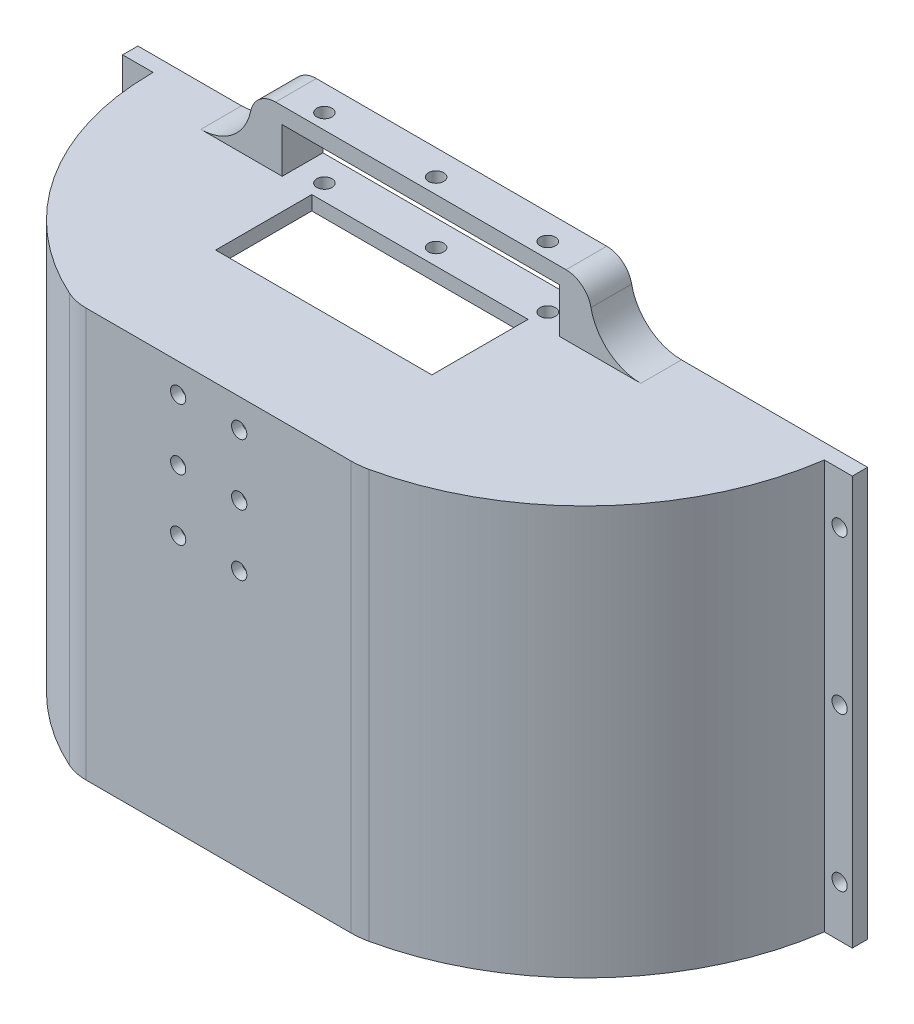
SolidWorks part; units mm, degrees
ref_plane "前视基准面" through (0, 0, 0) normal (0, 0, 1) x (1, 0, 0)
ref_plane "上视基准面" through (0, 0, 0) normal (0, 1, 0) x (1, 0, 0)
ref_plane "右视基准面" through (0, 0, 0) normal (1, 0, 0) x (0, 0, -1)
other "Configuration Table"
sketch "草图1" plane through (0, 0, 0) normal (0, 0, 1) x (1, 0, 0)
  line L0 (-77.3109, 43.4948) -> (-77.3109, -31.0552) construction
  line L1 (-77.3109, -31.0552) -> (50.1101, -31.0552) construction
  line L2 (50.1101, 43.4948) -> (-98.3152, 43.4948) construction
  line L3 (50.1101, -31.0552) -> (50.1101, 43.4948) construction
  line L4 (-85.3152, -34.0552) -> (58.1101, -34.0552)
  line L5 (58.1101, -34.0552) -> (58.1101, 46.2948)
  line L6 (58.1101, 46.2948) -> (-85.3152, 46.2948)
  line L7 (-85.3152, 46.2948) -> (-85.3152, -34.0552)
  line L8 (-85.3152, -34.0552) -> (58.1101, -34.0552)
  line L9 (58.1101, -34.0552) -> (58.1101, 46.2948)
  line L10 (58.1101, 46.2948) -> (-85.3152, 46.2948)
  line L11 (-85.3152, 46.2948) -> (-85.3152, -34.0552)
  line L12 (-77.3109, 43.4948) -> (-77.3109, -31.0552)
  line L13 (-77.3109, -31.0552) -> (50.1101, -31.0552)
  line L14 (50.1101, 43.4948) -> (-77.3109, 43.4948)
  line L15 (50.1101, -31.0552) -> (50.1101, 43.4948)
  circle A0 centre (55.6101, -24.0552) radius 1.5 construction
  circle A1 centre (55.6101, 6.1198) radius 1.5 construction
  circle A2 centre (55.6101, 36.2948) radius 1.5 construction
  circle A3 centre (-82.8109, -24.0552) radius 1.5 construction
  circle A4 centre (-82.8109, 6.1198) radius 1.5 construction
  circle A5 centre (-82.8109, 36.2948) radius 1.5 construction
  circle A6 centre (55.6101, -24.0552) radius 1.5
  circle A7 centre (55.6101, 6.1198) radius 1.5
  circle A8 centre (55.6101, 36.2948) radius 1.5
  circle A9 centre (-82.8109, -24.0552) radius 1.5
  circle A10 centre (-82.8109, 6.1198) radius 1.5
  circle A11 centre (-82.8109, 36.2948) radius 1.5
  dimension "D1" = 0
extrude "凸台-拉伸1" add sketch "草图1" along normal blind 3
sketch "草图2" plane through (0, 46.2948, 0) normal (0, 1, 0) x (1, 0, 0)
  line L0 (58.1101, -3) -> (-85.3152, -3) construction
  line L1 (52.1101, -3) -> (-79.3152, -3)
  line L2 (52.1101, -3) -> (52.1101, -8)
  line L3 (52.1101, -8) -> (-79.3152, -8)
  line L4 (-79.3152, -3) -> (-79.3152, -8)
  line L5 (58.1101, -3) -> (58.1101, 0) construction
  line L6 (-85.3152, -3) -> (-85.3152, 0) construction
  line L7 (-21.7025, -953.5) -> (-21.7025, 49046.5) construction
  line L8 (-52.0899, 46.5) -> (8.6848, 46.5) construction
  circle A0 centre (-21.7025, -5) radius 1.5
  point P15 (-21.7025, 46.5)
  dimension "D5" = 3
  dimension "D1" = 6
  dimension "D2" = 6
  dimension "D3" = 5
  dimension "D4" = 2
extrude "凸台-拉伸2" add sketch "草图2" against normal blind 2.8
sketch "草图3" plane through (0, 46.2948, 0) normal (0, 1, 0) x (1, 0, 0)
  line L0 (-999.7596, -5) -> (49000.2404, -5) construction
  circle A0 centre (0.2404, -5) radius 1.5
  circle A1 centre (-43.6455, -5) radius 1.5
  dimension "D1" = 3
  dimension "D2" = 3
extrude "切除-拉伸1" cut sketch "草图3" against normal blind 10
sketch "草图4" plane through (0, 46.2948, 0) normal (0, 1, 0) x (1, 0, 0)
  line L0 (-77.3109, 0) -> (50.1101, 0) construction
  line L1 (5.5404, 0) -> (11.5404, 0)
  line L2 (5.5404, 0) -> (5.5404, -8)
  line L3 (5.5404, -8) -> (11.5404, -8)
  line L4 (11.5404, 0) -> (11.5404, -8)
  line L5 (-79.3152, -8) -> (52.1101, -8) construction
  line L6 (5.2404, -16.5556) -> (5.2404, 0) construction
  line L7 (-48.9455, 0) -> (-54.9455, 0)
  line L8 (-48.9455, 0) -> (-48.9455, -8)
  line L9 (-48.9455, -8) -> (-54.9455, -8)
  line L10 (-54.9455, 0) -> (-54.9455, -8)
  line L11 (-48.6455, 0) -> (-48.6455, -16.5556) construction
  dimension "D1" = 6
  dimension "D2" = 6
  dimension "D3" = 0.3
  dimension "D4" = 0.3
extrude "凸台-拉伸3" add sketch "草图4" along normal blind 10
sketch "草图5" plane through (0, 56.2948, 0) normal (0, 1, 0) x (1, 0, 0)
  line L1 (5.5404, -8) -> (-48.9455, -8)
  line L2 (5.5404, -8) -> (5.5404, 0)
  line L3 (5.5404, 0) -> (-48.9455, 0)
  line L4 (-48.9455, -8) -> (-48.9455, 0)
extrude "凸台-拉伸4" add sketch "草图5" against normal blind 1.2
fillet "圆角1" radius 10 2 edges at (11.5404, 46.2948, 4) (-54.9455, 46.2948, 4)
sketch "草图6" plane through (0, 56.2948, 0) normal (0, 1, 0) x (1, 0, 0)
  circle A0 centre (0.2404, -5) radius 1.5
  circle A1 centre (-21.7025, -5) radius 1.5
  circle A2 centre (-43.6455, -5) radius 1.5
  dimension "D1" = 3
  dimension "D2" = 3
  dimension "D3" = 3
extrude "切除-拉伸2" cut sketch "草图6" against normal blind 3
sketch "草图7" plane through (0, 46.2948, 0) normal (0, 1, 0) x (1, 0, 0)
  line L0 (-47.8552, -50) -> (4.4502, -50) construction
  line L1 (-47.8552, -50) -> (4.4502, -50) construction
  line L2 (52.1101, -3) -> (-79.3152, -3)
  line L3 (-45.8212, -49.7) -> (3.801, -49.7)
  line L4 (-47.8552, -49.7) -> (4.4502, -49.7) construction
  arc A0 (52.1101, -3) -> (5.1618, -49.607) centre (-2.3222, 4.8814) cw
  arc A1 (-79.3152, -3) -> (-49.9475, -48.809) centre (-29.3159, -3.2641) ccw
  arc A2 (-45.8212, -49.7) -> (-49.9475, -48.809) centre (-45.8212, -39.7) cw
  arc A3 (3.801, -49.7) -> (5.1618, -49.607) centre (3.801, -39.7) ccw
  dimension "D2" = 55
  dimension "D3" = 50
  dimension "D4" = 10
  dimension "D5" = 10
  dimension "D6" = 48.3091
  dimension "D1" = 0.3
  dimension "D7" = 33.494
extrude "凸台-拉伸5" add sketch "草图7" against normal up to surface (2.8 mm away)
sketch "草图8" plane through (0, 46.2948, 0) normal (0, 1, 0) x (1, 0, 0)
  line L0 (52.1101, -3) -> (52.1101, -8) construction
  line L1 (52.1101, -8) -> (-79.3152, -8) construction
  line L2 (-79.3152, -3) -> (-79.3152, -8) construction
  line L3 (52.1101, -3) -> (52.1101, -8)
  line L4 (52.1101, -8) -> (51.148, -8)
  line L5 (-79.3152, -3) -> (-79.3152, -8)
  line L6 (-79.0911, -8) -> (-79.3152, -8)
  line L7 (-42.9375, -8.1913) -> (-42.9375, -19.0913) construction
  line L8 (-0.4375, -19.0913) -> (-42.9375, -19.0913) construction
  line L9 (-0.4375, -19.0913) -> (-0.4375, -8.1913)
  line L10 (-0.4375, -8.1913) -> (-42.9375, -8.1913)
  line L11 (-42.9375, -19.0913) -> (-42.9375, -8.1913)
  line L12 (-42.9375, -8.1913) -> (-0.4375, -8.1913) construction
  line L14 (-42.9375, -19.0913) -> (-0.4375, -19.0913) construction
  line L15 (-42.9375, -19.0913) -> (-42.9375, -27.0913)
  line L16 (-42.9375, -27.0913) -> (-0.4375, -27.0913)
  line L17 (-0.4375, -19.0913) -> (-0.4375, -27.0913)
  arc A0 (5.1618, -49.607) -> (52.1101, -3) centre (-2.3222, 4.8814) ccw construction
  arc A1 (-79.3152, -3) -> (-49.9475, -48.809) centre (-29.3159, -3.2641) ccw construction
  arc A2 (51.148, -8) -> (52.1101, -3) centre (-2.3222, 4.8814) ccw
  arc A3 (-79.3152, -3) -> (-79.0911, -8) centre (-29.3159, -3.2641) ccw
  circle A4 centre (0.2404, -5) radius 1.5 construction
  circle A5 centre (-43.6455, -5) radius 1.5 construction
  circle A6 centre (-21.7025, -5) radius 1.5 construction
  circle A7 centre (0.2404, -5) radius 1.5
  circle A8 centre (-43.6455, -5) radius 1.5
  circle A9 centre (-21.7025, -5) radius 1.5
  line M1 (52.1101, -8) -> (52.1101, -3)
  line M16 (-79.3152, -3.5282) -> (-79.3152, -8)
  line M17 (-79.3152, -8) -> (-79.0911, -8)
  line M23 (51.148, -8) -> (52.1101, -8)
  dimension "D1" = 3
  dimension "D2" = 3
  dimension "D3" = 3
  dimension "D4" = 8
extrude "切除-拉伸3" cut sketch "草图8" against normal blind 3 contours A2 M23 M1 | A3 M16 M17 | L11 L8 L9 L10 | A7 | A9 | A8
sketch "草图9" plane through (0, 43.4948, 0) normal (0, -1, 0) x (1, 0, 0)
  line L0 (-45.8212, 49.7) -> (3.801, 49.7) construction
  line L1 (-48.3212, 49.7) -> (6.2544, 49.7)
  line L2 (52.1101, 3) -> (-79.3152, 3) construction
  line L3 (52.6153, 3) -> (50.1101, 3)
  line L5 (-45.8212, 47.7) -> (3.801, 47.7)
  line L8 (52.1101, 3) -> (-79.3152, 3) construction
  line L9 (52.6847, 2.5) -> (-79.8101, 2.5) construction
  line L10 (49.7485, 5) -> (-77.2845, 5) construction
  line L11 (-77.2845, 5) -> (-77.2845, 3)
  line L12 (49.7485, 5) -> (50.1101, 3)
  line L13 (-77.2845, 3) -> (-79.8152, 3)
  line L14 (-45.8212, 50.2) -> (3.801, 50.2) construction
  line L15 (-45.8212, 49.7) -> (3.801, 49.7) construction
  arc A0 (5.1618, 49.607) -> (3.801, 49.7) centre (3.801, 39.7) ccw construction
  arc A1 (52.1101, 3) -> (5.1618, 49.607) centre (-2.3222, -4.8814) ccw construction
  arc A2 (-48.3212, 49.7) -> (-49.8596, 49.3923) centre (-48.3212, 45.7) ccw
  arc A3 (-49.9475, 48.809) -> (-79.3152, 3) centre (-29.3159, 3.2641) ccw construction
  arc A4 (5.1618, 49.607) -> (3.801, 49.7) centre (3.801, 39.7) ccw construction
  arc A5 (52.1101, 3) -> (5.1618, 49.607) centre (-2.3222, -4.8814) ccw construction
  arc A7 (-49.9475, 48.809) -> (-79.3152, 3) centre (-29.3159, 3.2641) ccw construction
  arc A8 (-49.1222, 46.9872) -> (-77.2845, 5) centre (-29.3159, 3.2641) ccw
  arc A9 (49.7485, 5) -> (4.8896, 47.6256) centre (-2.3222, -4.8814) ccw
  arc A10 (4.8896, 47.6256) -> (3.801, 47.7) centre (3.801, 39.7) ccw
  arc A11 (-45.8212, 47.7) -> (-49.1222, 46.9872) centre (-45.8212, 39.7) ccw
  arc A12 (-50.1538, 49.2644) -> (-79.8152, 3) centre (-29.3159, 3.2641) ccw
  arc A13 (52.6153, 3) -> (9.4309, 49.3598) centre (-2.3222, -4.8814) ccw
  arc A15 (-49.8596, 49.3923) -> (-50.1538, 49.2644) centre (-45.8212, 39.7) ccw
  arc A16 (52.6847, 2.5) -> (5.2298, 50.1023) centre (-2.3222, -4.8814) ccw construction
  arc A17 (-50.1538, 49.2644) -> (-79.8101, 2.5) centre (-29.3159, 3.2641) ccw construction
  arc A18 (5.2298, 50.1023) -> (3.801, 50.2) centre (3.801, 39.7) ccw construction
  arc A19 (-45.8212, 49.7) -> (-49.9475, 48.809) centre (-45.8212, 39.7) ccw construction
  arc A20 (-45.8212, 50.2) -> (-50.1538, 49.2644) centre (-45.8212, 39.7) ccw construction
  arc A21 (9.4309, 49.3598) -> (6.2544, 49.7) centre (6.2544, 34.7) ccw
  dimension "D3" = 8
  dimension "D4" = 4
  dimension "D5" = 15
  dimension "D1" = 2
  dimension "D2" = 0.5
extrude "凸台-拉伸6" add sketch "草图9" along normal up to surface and the other way blind 2.8
sketch "草图11" plane through (0, 0, 47.7) normal (0, 0, -1) x (-1, 0, 0)
  circle A0 centre (15.7025, 40.5948) radius 1.5
  circle A1 centre (27.7025, 40.5948) radius 1.5
  circle A2 centre (15.7025, 28.5948) radius 1.5
  circle A3 centre (27.7025, 28.5948) radius 1.4903
  circle A4 centre (27.7025, 16.5948) radius 1.5
  circle A5 centre (15.7025, 16.5948) radius 1.5
  dimension "D1" = 3
  dimension "D2" = 3
  dimension "D3" = 3
  dimension "D4" = 3
  dimension "D5" = 3
extrude "切除-拉伸4" cut sketch "草图11" against normal blind 3
sketch "草图12" plane through (0, -34.0552, 0) normal (0, -1, 0) x (1, 0, 0)
  line L0 (52.1101, 3) -> (-79.3152, 3) construction
  line L1 (-45.8212, 49.7) -> (6.2544, 49.7) construction
  line L2 (-45.8212, 49.7) -> (3.801, 49.7) construction
  line L3 (52.1101, 3) -> (-79.3152, 3)
  line L4 (-45.8212, 49.7) -> (6.2544, 49.7)
  line L5 (-45.8212, 49.7) -> (3.801, 49.7)
  line L6 (52.1101, 3) -> (52.6153, 3)
  arc A0 (52.6153, 3) -> (9.4309, 49.3598) centre (-2.3222, -4.8814) ccw construction
  arc A1 (9.4309, 49.3598) -> (6.2544, 49.7) centre (6.2544, 34.7) ccw construction
  arc A2 (-45.8212, 49.7) -> (-49.9475, 48.809) centre (-45.8212, 39.7) ccw construction
  arc A3 (-49.9475, 48.809) -> (-79.3152, 3) centre (-29.3159, 3.2641) ccw construction
  arc A4 (52.6153, 3) -> (9.4309, 49.3598) centre (-2.3222, -4.8814) ccw
  arc A5 (9.4309, 49.3598) -> (6.2544, 49.7) centre (6.2544, 34.7) ccw
  arc A6 (-45.8212, 49.7) -> (-49.9475, 48.809) centre (-45.8212, 39.7) ccw
  arc A7 (-49.9475, 48.809) -> (-79.3152, 3) centre (-29.3159, 3.2641) ccw
  line M1 (-79.3152, 3.5282) -> (-79.3152, 3)
  arc M7 (52.6153, 3) -> (9.4309, 49.3598) centre (-2.3222, -4.8814) ccw
  arc M8 (9.4309, 49.3598) -> (6.2544, 49.7) centre (6.2544, 34.7) ccw
  line M9 (6.2544, 49.7) -> (-45.8212, 49.7)
  arc M10 (-45.8212, 49.7) -> (-49.9475, 48.809) centre (-45.8212, 39.7) ccw
  arc M11 (-49.9475, 48.809) -> (-79.3152, 3.5282) centre (-29.3159, 3.2641) ccw
  line M12 (50.1101, 3) -> (-77.2845, 3)
  line M13 (-77.2845, 3) -> (-77.2845, 5)
  arc M14 (-77.2845, 5) -> (-49.1222, 46.9872) centre (-29.3159, 3.2641) cw
  arc M15 (-49.1222, 46.9872) -> (-45.8212, 47.7) centre (-45.8212, 39.7) cw
  line M16 (-45.8212, 47.7) -> (3.801, 47.7)
  arc M17 (3.801, 47.7) -> (4.8896, 47.6256) centre (3.801, 39.7) cw
  arc M18 (4.8896, 47.6256) -> (49.7485, 5) centre (-2.3222, -4.8814) cw
  line M19 (49.7485, 5) -> (50.1101, 3)
extrude "凸台-拉伸7" add sketch "草图12" against normal up to surface (3 mm away) contours M12 M19 M18 M17 M16 M15 M14 M13 | L3 L6 L4 M7 M8 M9 M10 M11 M1 M13 M14 M15 M16 M17 M18 M19 up to face at (-26.3372, -31.0552, 1.8)
sketch "草图13" plane through (0, 56.2948, 0) normal (0, 1, 0) x (1, 0, 0)
  line L4 (11.5404, 0) -> (-54.9455, 0)
  line L5 (-54.9455, 0) -> (-54.9455, -8)
  line L6 (-54.9455, -8) -> (11.5404, -8)
  line L7 (11.5404, -8) -> (11.5404, 0)
  line L8 (11.5404, 0) -> (-54.9455, 0)
  line L9 (-54.9455, 0) -> (-54.9455, -8)
  line L10 (-54.9455, -8) -> (11.5404, -8)
  line L11 (11.5404, -8) -> (11.5404, 0)
  circle A0 centre (-43.6455, -5) radius 1.5 construction
  circle A1 centre (-21.7025, -5) radius 1.5 construction
  circle A2 centre (0.2404, -5) radius 1.5 construction
  circle A3 centre (-43.6455, -5) radius 1.5
  circle A4 centre (-21.7025, -5) radius 1.5
  circle A5 centre (0.2404, -5) radius 1.5
  dimension "D1" = 0
extrude "凸台-拉伸8" add sketch "草图13" along normal blind 2
fillet "圆角2" radius 5 2 edges at (-54.9455, 58.2948, 4) (11.5404, 58.2948, 4)
